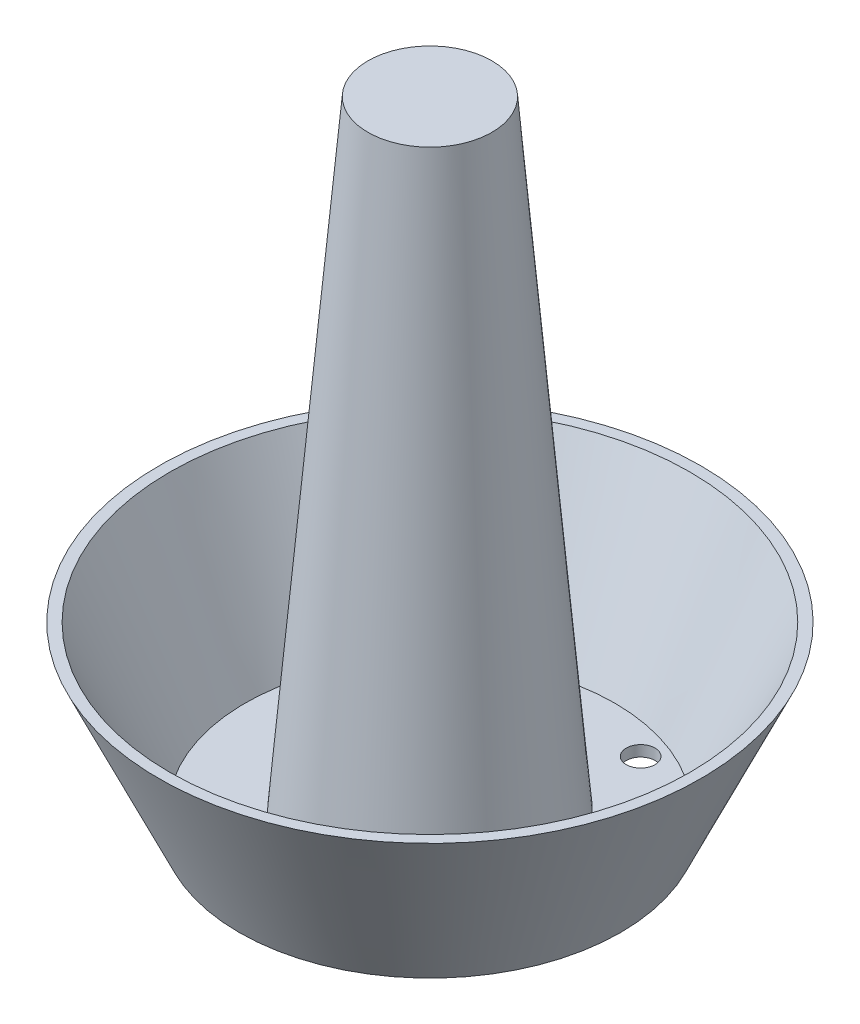
SolidWorks part; units mm, degrees
ref_plane "Front" through (0, 0, 0) normal (0, 0, 1) x (1, 0, 0)
ref_plane "Top" through (0, 0, 0) normal (0, 1, 0) x (1, 0, 0)
ref_plane "Right" through (0, 0, 0) normal (1, 0, 0) x (0, 0, -1)
sketch "Sketch1" plane through (0, 0, 0) normal (0, 0, 1) x (1, 0, 0)
  line L0 (0, 184.15) -> (18.161, 184.15)
  line L1 (0, -50) -> (0, 50) construction
  line L2 (18.161, 184.15) -> (33.655, 3.175)
  line L3 (33.655, 3.175) -> (54.1734, 3.175)
  line L4 (54.1734, 3.175) -> (76.2, 50.8)
  line L5 (76.2, 50.8) -> (79.375, 50.8)
  line L6 (79.375, 50.8) -> (55.88, 0)
  line L7 (50, 0) -> (-50, 0) construction
  line L8 (55.88, 0) -> (0, 0)
  line L9 (0, 0) -> (0, 184.15)
  dimension "D1" = 184.15
  dimension "D2" = 3.175
  dimension "D3" = 50.8
  dimension "D4" = 55.88
  dimension "D5" = 3.175
  dimension "D6" = 18.161
  dimension "D7" = 79.375
  dimension "D8" = 33.655
revolve "Revolve1" add sketch "Sketch1" angle 360 about L9
sketch "Sketch4" plane through (0, 0, 0) normal (0, -1, 0) x (1, 0, 0)
  line L0 (0, 0) -> (0, 44.45) construction
  line L1 (0, 44.45) -> (17.272, 44.45) construction
  line L2 (0, 44.45) -> (-17.272, 44.45) construction
  dimension "D1" = 34.544
  dimension "D2" = 44.45
hole_wizard "5/16 Clearance Hole1" positions "Sketch6" profile "Sketch5" hole size "5/16" standard "ANSI Inch" end condition through all
sketch "Sketch6" plane through (0, 0, 0) normal (0, -1, 0) x (-1, 0, 0)
  point P0 (17.272, -44.45)
  point P3 (-17.272, -44.45)
sketch "Sketch5" plane through (-17.272, 0, 44.45) normal (1, 0, 0) x (0, 0, -1)
  line L0 (0, 0) -> (0, 184.15)
  line L1 (0, 184.15) -> (4.2164, 184.15)
  line L2 (4.2164, 184.15) -> (4.2164, 0)
  line L5 (4.2164, 0) -> (0, 0)
  line L11 (0, -6.35) -> (0, 107.95) construction
  dimension "Thru Hole Dia." = 8.4328
  dimension "Thru Hole Depth" = 184.15
sketch "Sketch2" plane through (0, 0, 0) normal (0, -1, 0) x (1, 0, 0)
  line L0 (0, 0) -> (-14.986, 0) construction
  circle A0 centre (-14.986, 0) radius 5.461
  dimension "D1" = 10.922
  dimension "D2" = 14.986
extrude "RF Connector" add sketch "Sketch2" along normal blind 12.7
mirror "Mirror1" about plane through (0, 0, 0) normal (0, 0, 1) of "5/16 Clearance Hole1"
sketch "Sketch7" plane through (0, 0, 0) normal (0, -1, 0) x (1, 0, 0)
  line L1 (19.558, -19.558) -> (-19.558, -19.558) construction
  line L2 (19.558, -19.558) -> (19.558, 19.558) construction
  line L3 (19.558, 19.558) -> (-19.558, 19.558) construction
  line L4 (-19.558, -19.558) -> (-19.558, 19.558) construction
  line L5 (19.558, -19.558) -> (-19.558, 19.558) construction
  line L6 (19.558, 19.558) -> (-19.558, -19.558) construction
  circle A0 centre (-19.558, -19.558) radius 4.318
  circle A1 centre (0, 0) radius 4.318
  circle A2 centre (-19.558, 19.558) radius 4.318
  circle A3 centre (19.558, 19.558) radius 4.318
  circle A4 centre (19.558, -19.558) radius 4.318
  point P0 (0, 0)
  dimension "D2" = 8.636
  dimension "D1" = 39.116
extrude "Boss-Extrude1" add sketch "Sketch7" along normal blind 4.572
